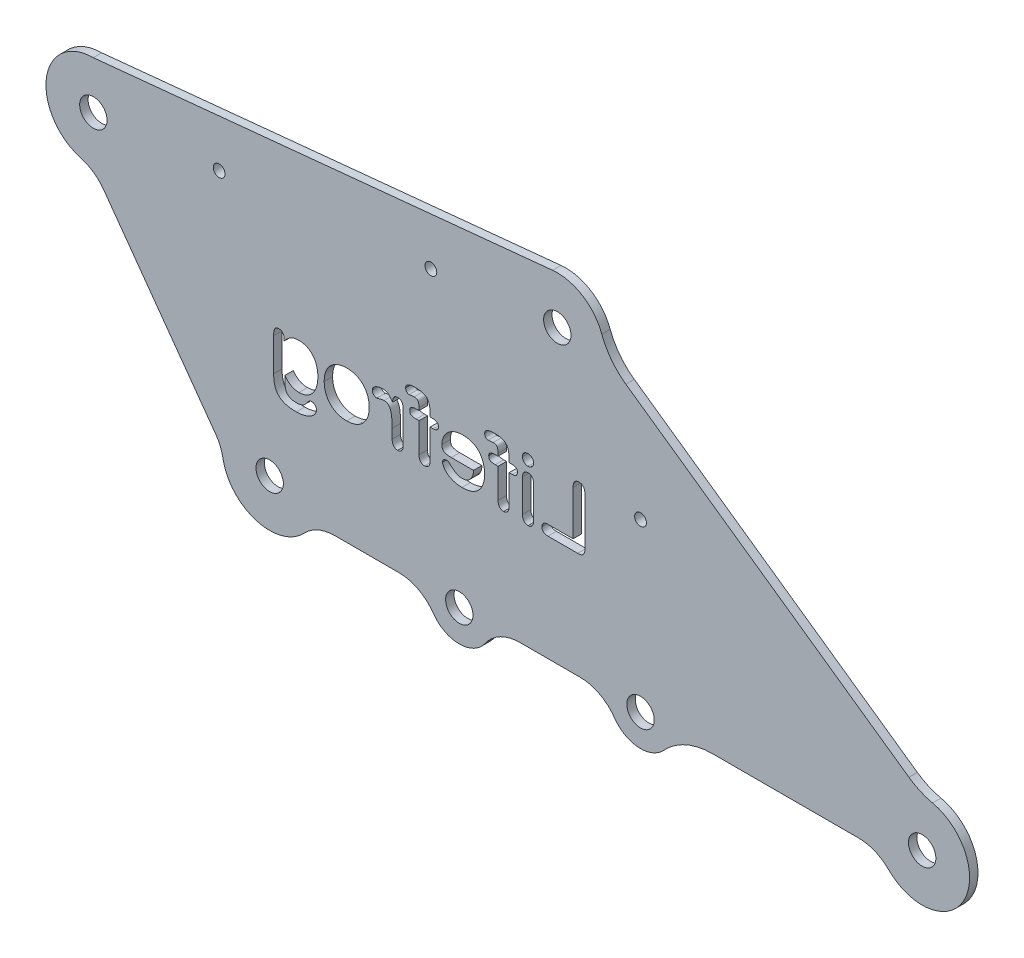
SolidWorks part; units mm, degrees
ref_plane "Front Plane" through (0, 0, 0) normal (0, 0, 1) x (1, 0, 0)
ref_plane "Top Plane" through (0, 0, 0) normal (0, 1, 0) x (1, 0, 0)
ref_plane "Right Plane" through (0, 0, 0) normal (1, 0, 0) x (0, 0, -1)
sketch "Sketch2" plane through (0, 0, 0) normal (0, 0, 1) x (1, 0, 0)
  line L0 (-96.303, -40.0195) -> (103.697, -40.0195) construction
  line L1 (56.1417, 22.4699) -> (-27.5885, 22.4699) construction
  line L2 (56.1417, 22.4699) -> (56.1417, -53.9544) construction
  line L3 (56.1417, -53.9544) -> (-159.2025, -53.9544) construction
  line L4 (-159.2025, 22.4699) -> (-159.2025, -53.9544) construction
  line L5 (-96.303, -40.0195) -> (-53.2713, -40.0195) construction
  line L6 (-100.4268, -47.0897) -> (-100.4268, -59.5897) construction
  line L7 (-100.4268, -59.5897) -> (73.7025, -59.5897) construction
  line L8 (-100.4268, -59.5897) -> (-302.9325, -59.5897) construction
  line L9 (-62.0853, -59.5897) -> (-73.2496, -62.9155) construction
  line L10 (-19.0853, -47.0897) -> (-15.8353, -47.0897) construction
  line L11 (47.7386, -47.0897) -> (47.7386, -41.2921) construction
  line L12 (-62.0853, -47.0897) -> (-107.0853, -47.0897) construction
  line L13 (-107.0853, -47.0897) -> (-107.0853, -42.5195) construction
  line L14 (-62.0853, -47.0897) -> (-58.8353, -47.0897) construction
  line L15 (-167.9726, 11.2199) -> (-124.5853, -42.5195) construction
  line L16 (-124.5853, -42.5195) -> (-167.9726, -37.8951) construction
  line L17 (-167.9726, -37.8951) -> (-167.9726, 11.2199) construction
  line L18 (-167.9726, -37.8951) -> (-167.9726, -59.5897) construction
  line L19 (-146.4823, -3.4151) -> (-119.9002, -40.3454)
  line L21 (-148.9187, 22.4699) -> (-39.9417, 33.2746)
  line L24 (-22.5647, 18.5545) -> (44.5996, -28.6343)
  line L25 (11.3122, -40.0195) -> (103.697, -40.0195) construction
  line L26 (-41.384, 22.4699) -> (-159.2025, 22.4699) construction
  line L27 (-47.7239, -47.0897) -> (-33.4467, -47.0897)
  line L28 (-1.9905, -47.0897) -> (32.6866, -47.0897)
  line L29 (-76.4467, -47.0897) -> (-91.6169, -47.0897)
  line L30 (-54.5853, -47.0897) -> (-19.0853, -47.0897) construction
  line L31 (-11.5853, -47.0897) -> (47.7386, -47.0897) construction
  line L32 (-148.9187, 11.2199) -> (-38.8318, 22.0795) construction
  arc A0 (-26.3612, 21.2219) -> (-51.3257, 22.4699) centre (-38.8318, 22.0795) ccw construction
  circle A1 centre (-38.8318, 22.0795) radius 3.25 construction
  arc A2 (-74.5853, -47.0897) -> (-51.639, -53.9544) centre (-62.0853, -47.0897) ccw construction
  circle A3 centre (-62.0853, -47.0897) radius 3.25 construction
  circle A4 centre (47.7386, -42.0897) radius 3.25
  circle A5 centre (-19.0853, -47.0897) radius 3.25 construction
  circle A6 centre (47.7386, -42.0897) radius 17.5 construction
  circle A7 centre (47.7386, -42.0897) radius 3.25 construction
  circle A8 centre (-107.0853, -42.5195) radius 17.5 construction
  circle A9 centre (-107.0853, -42.5195) radius 3.25 construction
  circle A10 centre (-148.9187, 11.2199) radius 19.0539 construction
  circle A11 centre (-148.9187, 11.2199) radius 3.25 construction
  arc A12 (-148.9187, 22.4699) -> (-151.9256, 0.3791) centre (-148.9187, 11.2199) ccw
  arc A13 (-118.1664, -44.4613) -> (-98.8961, -50.2332) centre (-107.0853, -42.5195) ccw
  arc A14 (-28.2784, 25.9769) -> (-39.9417, 33.2746) centre (-38.8318, 22.0795) ccw
  arc A15 (-68.2402, -51.3754) -> (-55.9304, -51.3754) centre (-62.0853, -47.0897) ccw
  arc A16 (-25.2402, -51.3754) -> (-13.5666, -52.1685) centre (-19.0853, -47.0897) ccw
  arc A17 (39.7699, -50.0309) -> (50.2007, -31.1125) centre (47.7386, -42.0897) ccw
  arc A18 (-7.7098, -42.5525) -> (-9.0853, -40.0195) centre (-19.0853, -47.0897) ccw construction
  arc A19 (-31.8119, -47.0897) -> (-8.3689, -53.9544) centre (-19.0853, -47.0897) ccw construction
  circle A20 centre (-19.0853, -47.0897) radius 3.25
  circle A21 centre (-62.0853, -47.0897) radius 3.25
  circle A22 centre (-107.0853, -42.5195) radius 3.25
  circle A23 centre (-148.9187, 11.2199) radius 3.25
  circle A24 centre (-38.8318, 22.0795) radius 3.25
  arc A25 (32.6866, -47.0897) -> (39.7699, -50.0309) centre (32.6866, -57.0897) cw
  arc A26 (-146.4823, -3.4151) -> (-151.9256, 0.3791) centre (-154.5984, -9.257) ccw
  arc A27 (-119.9002, -40.3454) -> (-118.1664, -44.4613) centre (-128.0164, -46.1873) cw
  arc A28 (-91.6169, -47.0897) -> (-98.8961, -50.2332) centre (-91.6169, -57.0897) ccw
  arc A29 (-76.4467, -47.0897) -> (-68.2402, -51.3754) centre (-76.4467, -57.0897) cw
  arc A30 (-33.4467, -47.0897) -> (-25.2402, -51.3754) centre (-33.4467, -57.0897) cw
  arc A31 (-47.7239, -47.0897) -> (-55.9304, -51.3754) centre (-47.7239, -57.0897) ccw
  arc A33 (-22.5647, 18.5545) -> (-28.2784, 25.9769) centre (-13.5206, 31.4271) cw
  arc A34 (44.5996, -28.6343) -> (50.2007, -31.1125) centre (53.6437, -15.7617) ccw
  arc A35 (-1.9905, -47.0897) -> (-13.5666, -52.1685) centre (-1.9905, -62.8218) ccw
  point P39 (39.7051, -42.5361)
  point P67 (37.6608, -47.0897)
  point P70 (-148.9187, -0.0301)
  point P73 (-118.3353, -42.5195)
  point P76 (-96.8054, -47.0897)
  point P79 (-69.5853, -47.0897)
  point P82 (-26.5853, -47.0897)
  point P87 (47.7386, -42.5525)
  point P91 (-27.5818, 22.0795)
  point P94 (47.7386, -30.8397)
  dimension "D1" = 25
  dimension "D2" = 6.5
  dimension "D5" = 35
  dimension "D6" = 6.5
  dimension "D10" = 22.5
  dimension "D11" = 22.5
  dimension "D12" = 22.5
  dimension "D13" = 6.5
  dimension "D14" = 6.5
  dimension "D15" = 15
  dimension "D16" = 15
  dimension "D17" = 22.5
  dimension "D18" = 10
  dimension "D3" = 20
  dimension "D4" = 0
  dimension "D7" = 45
  dimension "D8" = 43
  dimension "D9" = 45
extrude "Boss-Extrude1" add sketch "Sketch2" along normal blind 2
sketch "Sketch5" plane through (0, 0, 2) normal (0, 0, 1) x (1, 0, 0)
  line L1 (-106.4284, -21.9146) -> (-30.7738, -21.9146) construction
  line L2 (-106.4284, -21.9146) -> (-106.4284, -6.1743) construction
  line L3 (-106.4284, -6.1743) -> (-30.7738, -6.1743) construction
  line L4 (-30.7738, -21.9146) -> (-30.7738, -6.1743) construction
sketch "Sketch7" plane through (0, 0, 2) normal (0, 0, 1) x (1, 0, 0)
  line L0 (-148.9187, 11.2199) -> (-38.8318, 22.0795) construction
  line L1 (-148.9187, 11.2199) -> (-107.0853, -42.5195) construction
  line L2 (-107.0853, -42.5195) -> (25.9147, -42.5195) construction
  line L3 (25.9147, -42.5195) -> (-38.8318, 22.0795) construction
  line L5 (-107.0853, -2.5195) -> (-35.0853, -2.5195) construction
  line L6 (25.9147, -42.5195) -> (25.9147, -7.5195) construction
  line L7 (25.9147, -7.5195) -> (-64.0853, -7.5195) construction
  circle A0 centre (-119.0636, 14.1649) radius 1.4
  circle A1 centre (-68.8318, 19.1201) radius 1.4
  circle A5 centre (-19.0853, -7.5195) radius 1.4
  dimension "D1" = 2.8
  dimension "D2" = 2.8
  dimension "D4" = 30
  dimension "D5" = 2.8
  dimension "D6" = 40
  dimension "D3" = 30
  dimension "D7" = 35
  dimension "D9" = 45
extrude "Cut-Extrude4" cut sketch "Sketch7" against normal through all
sketch "Sketch8" plane through (0, 0, 0) normal (0, 0, -1) x (-1, 0, 0)
  text T0 "Lifefrog" font "Arial Rounded MT Bold" height 15
extrude "Cut-Extrude5" cut sketch "Sketch8" against normal through all
sketch "Sketch9" plane through (0, 0, 0) normal (0, 0, -1) x (-1, 0, 0)
  line L0 (59.4615, -14.7017) -> (62.4003, -14.7017) construction
  line L1 (59.4615, -12.7672) -> (62.4003, -12.7672)
  line L2 (59.4615, -16.6363) -> (62.4003, -16.6363)
  arc A0 (59.4615, -12.7672) -> (59.4615, -16.6363) centre (59.4615, -14.7017) ccw
  arc A1 (62.4003, -16.6363) -> (62.4003, -12.7672) centre (62.4003, -14.7017) ccw
  circle A2 centre (88.4097, -16.6363) radius 4.4245
  circle A3 centre (101.377, -16.6363) radius 3.8005
  point P2 (60.9309, -14.7017)
extrude "Cut-Extrude6" cut sketch "Sketch9" against normal blind 10
